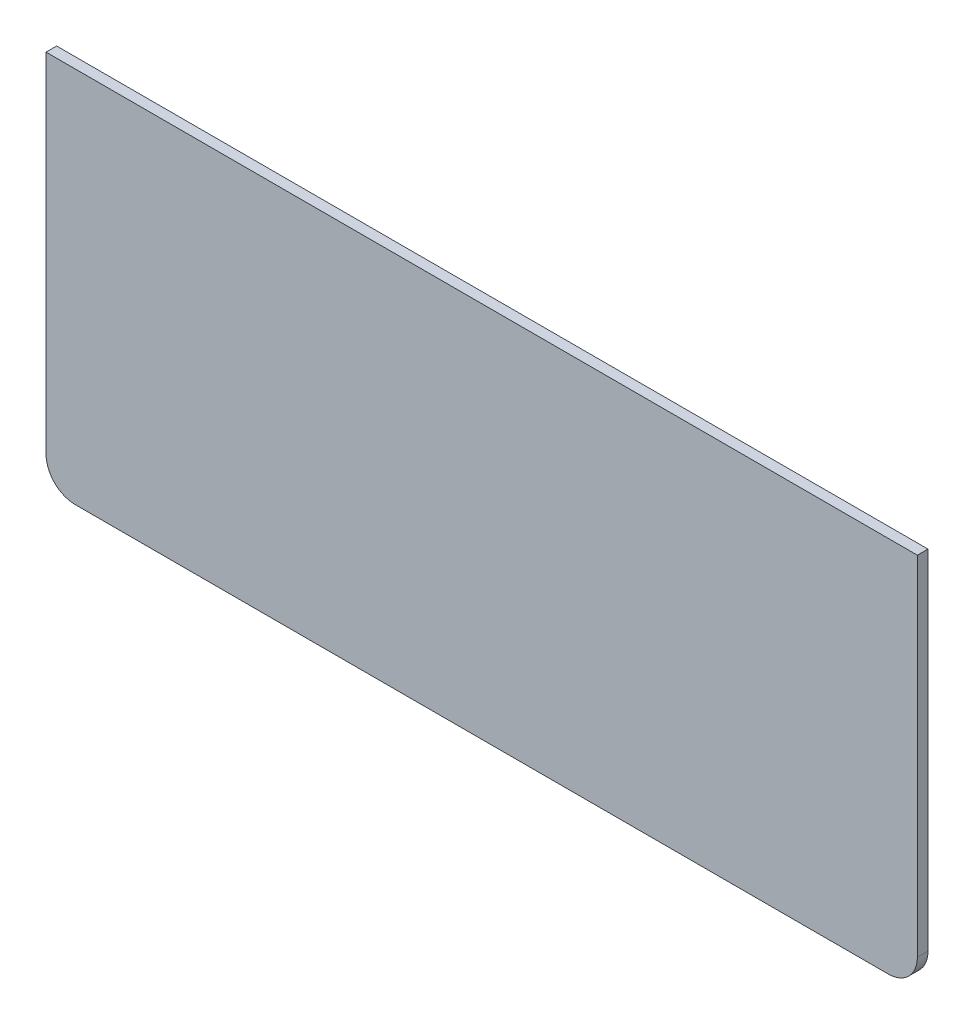
SolidWorks part; units mm, degrees
material "5052-H32"
ref_plane "Front Plane" through (0, 0, 0) normal (0, 0, 1) x (1, 0, 0)
ref_plane "Top Plane" through (0, 0, 0) normal (0, 1, 0) x (1, 0, 0)
ref_plane "Right Plane" through (0, 0, 0) normal (1, 0, 0) x (0, 0, -1)
sketch "Sketch2" plane through (0, 0, 0) normal (0, 0, 1) x (1, 0, 0)
  line L0 (-53.5866, 40.5355) -> (207.7634, 40.5355)
  line L1 (207.7634, 40.5355) -> (207.7634, -72.6395)
  line L2 (207.7634, -72.6395) -> (-53.5866, -72.6395)
  line L3 (-53.5866, -72.6395) -> (-53.5866, 40.5355)
  dimension "D1" = 113.175
  dimension "D2" = 261.35
extrude "Boss-Extrude1" add sketch "Sketch2" along normal blind 3.175
fillet "Fillet1" radius 8.7312 2 edges at (-53.5866, -72.6395, 1.5875) (207.7634, -72.6395, 1.5875)
equation "\"L\"= 420mm"
equation "\"W\"= 255mm"
equation "\"H\"= 110mm"
equation "\"Compartment Width\"= 80"
equation "\"T\"= 4.7625 * 2 / 3mm"
equation "\"Inside Fillet Radius\"= 5.55625mm"
equation "\"D1@Fillet1\"=\"Inside Fillet Radius\"+\"T\""
equation "\"D1@Sketch2\"=\"T\"+\"H\""
equation "\"D2@Sketch2\"=2*\"T\"+\"W\""
equation "\"D1@Boss-Extrude1\"=\"T\""
equation "\"Offset\"= 16mm"
equation "\"Hole\"=25mm"
equation "\"Wheel to Wall\"= 43"
